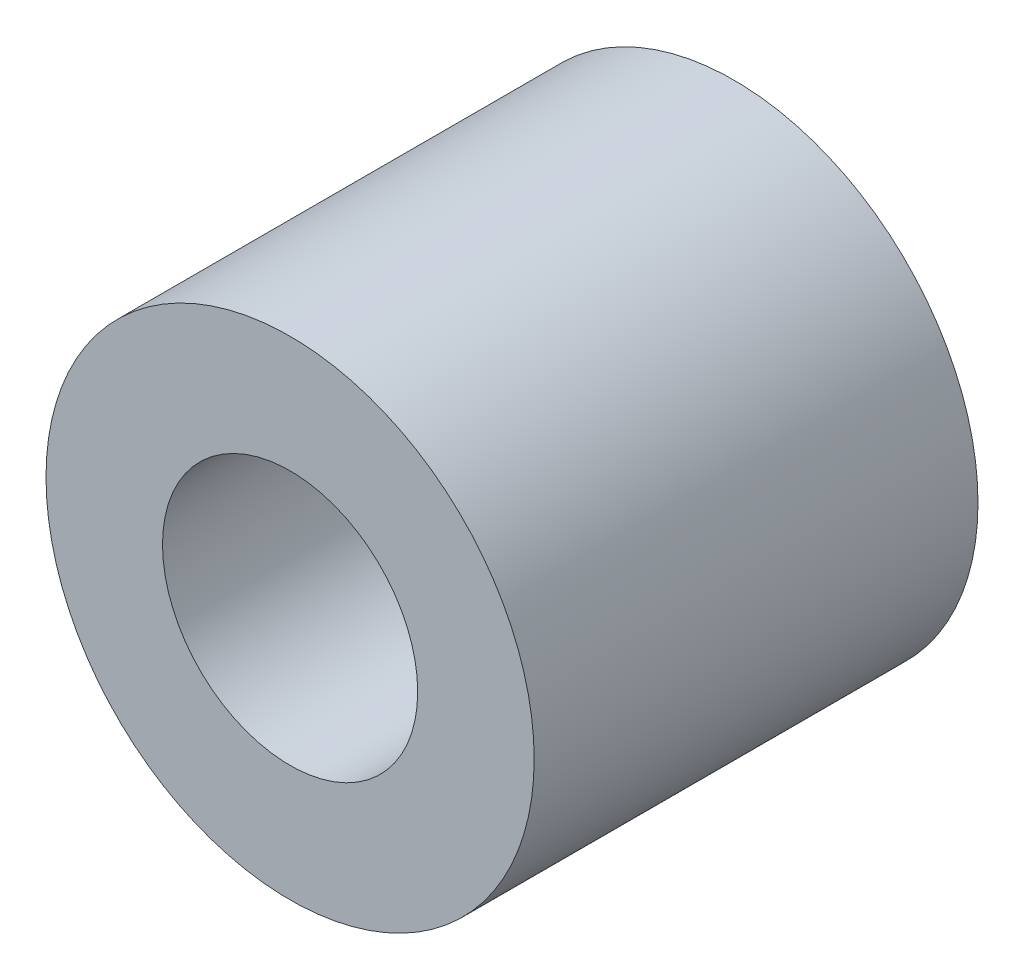
SolidWorks part; units mm, degrees
ref_plane "前视基准面" through (0, 0, 0) normal (0, 0, 1) x (1, 0, 0)
ref_plane "上视基准面" through (0, 0, 0) normal (0, 1, 0) x (1, 0, 0)
ref_plane "右视基准面" through (0, 0, 0) normal (1, 0, 0) x (0, 0, -1)
sketch "草图1" plane through (0, 0, 0) normal (0, 0, 1) x (1, 0, 0)
  circle A0 centre (0, 0) radius 1.15
  circle A1 centre (0, 0) radius 2.2
extrude "凸台-拉伸2" add sketch "草图1" along normal blind 4
